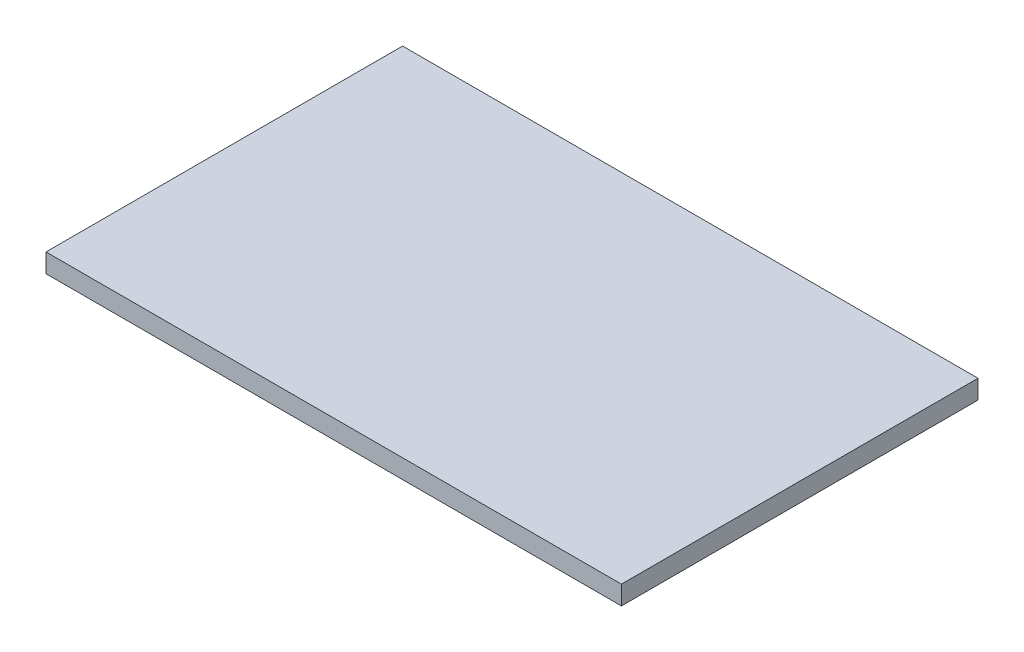
SolidWorks part; units mm, degrees
ref_plane "Front Plane" through (0, 0, 0) normal (0, 0, 1) x (1, 0, 0)
ref_plane "Top Plane" through (0, 0, 0) normal (0, 1, 0) x (1, 0, 0)
ref_plane "Right Plane" through (0, 0, 0) normal (1, 0, 0) x (0, 0, -1)
sketch "Sketch1" plane through (0, 0, 0) normal (0, 1, 0) x (1, 0, 0)
  line L1 (48.41, 30) -> (-48.41, 30)
  line L2 (48.41, 30) -> (48.41, -30)
  line L3 (48.41, -30) -> (-48.41, -30)
  line L4 (-48.41, 30) -> (-48.41, -30)
  line L5 (48.41, 30) -> (-48.41, -30) construction
  line L6 (48.41, -30) -> (-48.41, 30) construction
  point P0 (0, 0)
  dimension "D1" = 60
  dimension "D2" = 96.82
extrude "Boss-Extrude1" add sketch "Sketch1" along normal blind 3.18 contours L2 L1 L4 L3
sketch "Sketch2" plane through (0, 3.18, 0) normal (0, 1, 0) x (1, 0, 0)
  line L0 (48.41, -30) -> (48.41, 30) construction
  line L1 (-48.41, -30) -> (48.41, -30) construction
  line L2 (18.41, 0) -> (18.41, 48.3) construction
  circle A0 centre (-33.99, 33) radius 1.6
  circle A1 centre (-33.99, 5.1) radius 1.6
  circle A2 centre (16.81, 48.3) radius 1.6
  circle A3 centre (18.41, 0) radius 1.6
  dimension "D1" = 3.2
  dimension "D2" = 50.8
  dimension "D3" = 27.9
  dimension "D7" = 5.1
  dimension "D4" = 48.3
  dimension "D5" = 30
  dimension "D6" = 30
extrude "Cut-Extrude1" [suppressed] cut sketch "Sketch2" against normal through all
sketch "Sketch3" [suppressed] plane through (0, 0, 0) normal (0, -1, 0) x (1, 0, 0)
  line L0 (0, -1.2222) -> (0, -24.0948) construction
  line L1 (-13.75, -6.5) -> (13.75, -6.5) construction
  line L2 (50, 30) -> (-50, 30) construction
  circle A0 centre (-13.75, -6.5) radius 2
  circle A1 centre (13.75, -6.5) radius 2
  circle A2 centre (0, 15) radius 2
  dimension "D1" = 4
  dimension "D2" = 27.5
  dimension "D3" = 15
  dimension "D4" = 21.5
extrude "Cut-Extrude2" [suppressed] cut sketch "Sketch3" against normal blind 10
ref_plane "Plane1" through (-50, 66.36, -50) normal (0, 0, 1) x (1, 0, 0)
sketch "Sketch5" plane through (0, 0, 0) normal (0, -1, 0) x (1, 0, 0)
  line L0 (0, 0) -> (38.0998, 0) construction
  line L1 (29.5493, -10.8537) -> (29.5493, 18.3981) construction
  line L3 (-35.4792, 12.1463) -> (-22.9792, 12.1463)
  line L4 (-35.4792, 12.1463) -> (-35.4792, -10.8537)
  line L5 (-35.4792, -10.8537) -> (-22.9792, -10.8537)
  line L6 (-22.9792, 12.1463) -> (-22.9792, -10.8537)
  line L7 (-35.4792, 12.1463) -> (-22.9792, -10.8537) construction
  line L8 (-35.4792, -10.8537) -> (-22.9792, 12.1463) construction
  circle A0 centre (29.5493, -18.3981) radius 3.81
  circle A1 centre (29.5493, 18.3981) radius 3.81
  point P9 (-29.2292, 0.6463)
  dimension "D1" = 7.62
  dimension "D2" = 12.5
  dimension "D3" = 23
extrude "Cut-Extrude3" [suppressed] cut sketch "Sketch5" against normal blind 10
